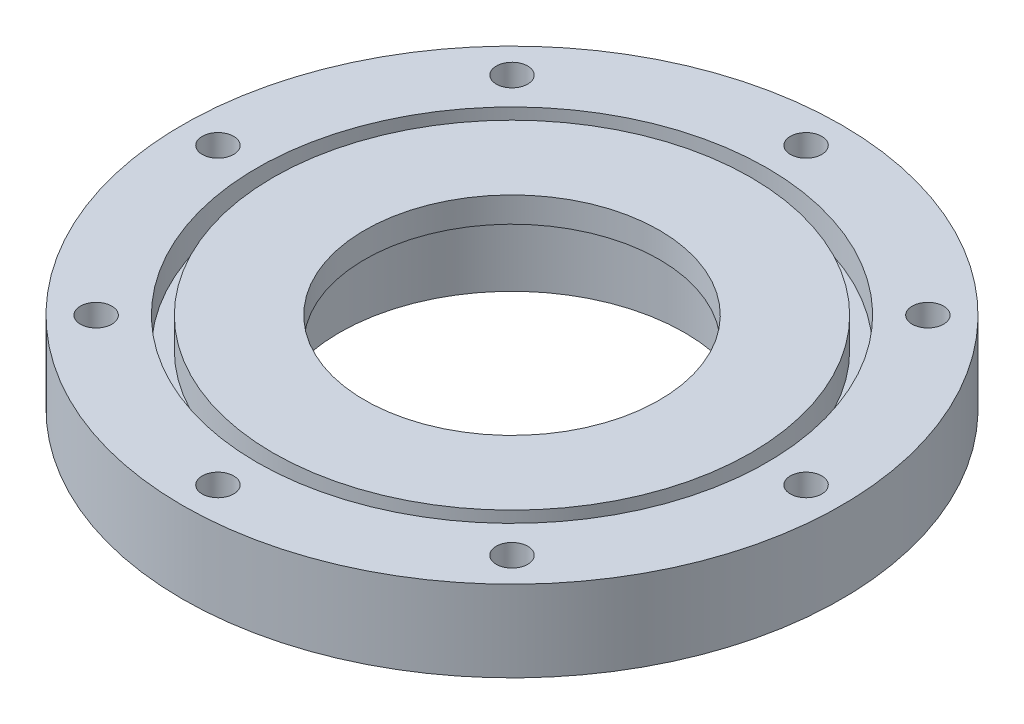
SolidWorks part; units mm, degrees
material "PVC rigide"
ref_plane "Plan de face" through (0, 0, 0) normal (0, 0, 1) x (1, 0, 0)
ref_plane "Plan de dessus" through (0, 0, 0) normal (0, 1, 0) x (1, 0, 0)
ref_plane "Plan de droite" through (0, 0, 0) normal (1, 0, 0) x (0, 0, -1)
sketch "Esquisse1" plane through (0, 0, 0) normal (0, 0, 1) x (1, 0, 0)
  line L0 (0, 0) -> (0, 40.6897) construction
  line L1 (-34.05, 0) -> (-34.05, 15)
  line L2 (-34.05, 15) -> (-29.05, 15)
  line L3 (-29.05, 15) -> (-29.05, 20)
  line L4 (-29.05, 20) -> (-47.1, 20)
  line L5 (-47.1, 20) -> (-47.1, 14)
  line L6 (-47.1, 14) -> (-50.3, 14)
  line L7 (-50.3, 14) -> (-50.3, 20)
  line L8 (-50.3, 20) -> (-65, 20)
  line L9 (-65, 20) -> (-65, 0)
  line L10 (-65, 0) -> (-34.05, 0)
  line L11 (-57.65, 20) -> (-57.65, 0) construction
  point P15 (-50.3, 17.0814)
  dimension "D1" = 20
  dimension "D2" = 5
  dimension "D3" = 68.1
  dimension "D4" = 5
  dimension "D5" = 94.2
  dimension "D6" = 100.6
  dimension "D7" = 130
  dimension "D8" = 14.7
  dimension "D9" = 6
revolve "Révolution1" add sketch "Esquisse1" angle 360 about L0
sketch "Esquisse2" plane through (0, 0, 0) normal (0, -1, 0) x (1, 0, 0)
  line L0 (0, 0) -> (0, 65) construction
  circle A0 centre (0, 0) radius 65 construction
  circle A1 centre (0, 58) radius 3.1
  circle A2 centre (41.0122, 41.0122) radius 3.1
  circle A3 centre (58, 0) radius 3.1
  circle A4 centre (41.0122, -41.0122) radius 3.1
  circle A5 centre (0, -58) radius 3.1
  circle A6 centre (-41.0122, -41.0122) radius 3.1
  circle A7 centre (-58, 0) radius 3.1
  circle A8 centre (-41.0122, 41.0122) radius 3.1
  dimension "D2" = 6.2
  dimension "D1" = 58
  dimension "D3" = 8
extrude "Enlèv. mat.-Extru.1" cut sketch "Esquisse2" against normal through all
sketch "Esquisse4" plane through (0, 0, 0) normal (0, -1, 0) x (1, 0, 0)
  circle A0 centre (0, 0) radius 42.05
  circle A1 centre (0, 0) radius 34.05 construction
  dimension "D1" = 8
extrude "Enlèv. mat.-Extru.3" cut sketch "Esquisse4" against normal blind 4 flip side to cut
sketch "Esquisse3" plane through (0, 4, 0) normal (0, -1, 0) x (1, 0, 0)
  circle A0 centre (0, 58) radius 5.1
  circle A1 centre (41.0122, 41.0122) radius 5.1
  circle A2 centre (58, 0) radius 5.1
  circle A3 centre (41.0122, -41.0122) radius 5.1
  circle A4 centre (0, -58) radius 5.1
  circle A5 centre (-41.0122, -41.0122) radius 5.1
  circle A6 centre (-58, 0) radius 5.1
  circle A7 centre (-41.0122, 41.0122) radius 5.1
  dimension "D1" = 10.2
  dimension "D2" = 8
extrude "Enlèv. mat.-Extru.2" cut sketch "Esquisse3" against normal blind 6.2
